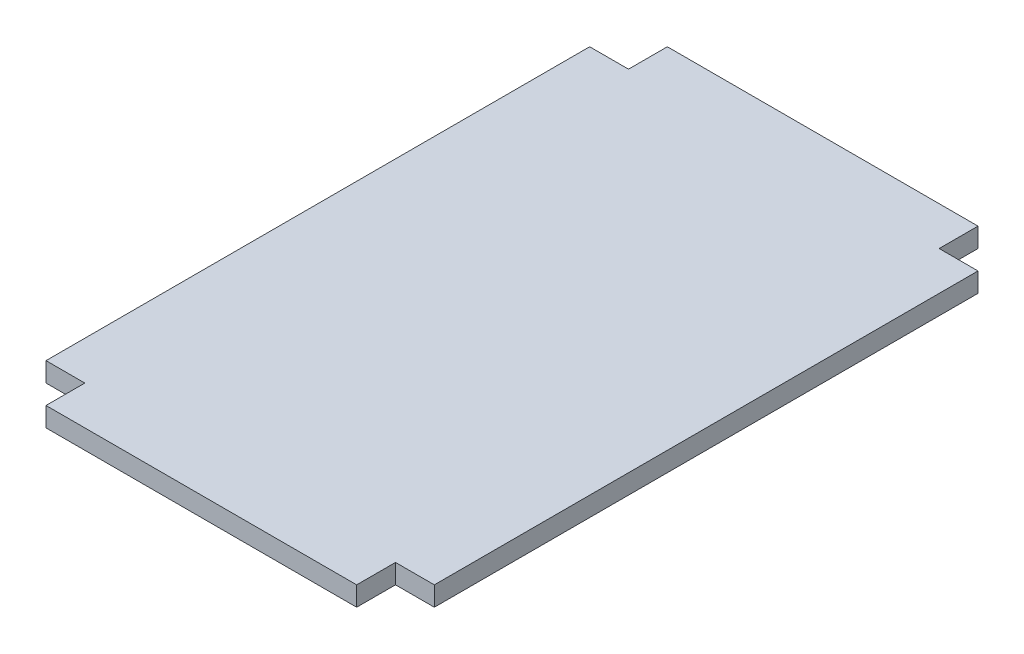
SolidWorks part; units mm, degrees
material "Oak"
ref_plane "Front Plane" through (0, 0, 0) normal (0, 0, 1) x (1, 0, 0)
ref_plane "Top Plane" through (0, 0, 0) normal (0, 1, 0) x (1, 0, 0)
ref_plane "Right Plane" through (0, 0, 0) normal (1, 0, 0) x (0, 0, -1)
sketch "Sketch1" plane through (0, 0, 0) normal (0, 1, 0) x (1, 0, 0)
  line L0 (-194.7505, 375.2161) -> (-194.7505, -158.1839)
  line L1 (-194.7505, -158.1839) -> (-156.6505, -158.1839)
  line L2 (-156.6505, -158.1839) -> (-156.6505, -196.2839)
  line L3 (-156.6505, -196.2839) -> (148.1495, -196.2839)
  line L4 (148.1495, -196.2839) -> (148.1495, -158.1839)
  line L5 (148.1495, -158.1839) -> (186.2495, -158.1839)
  line L6 (186.2495, -158.1839) -> (186.2495, 375.2161)
  line L7 (186.2495, 375.2161) -> (148.1495, 375.2161)
  line L8 (148.1495, 375.2161) -> (148.1495, 413.3161)
  line L9 (148.1495, 413.3161) -> (-156.6505, 413.3161)
  line L10 (-156.6505, 413.3161) -> (-156.6505, 375.2161)
  line L11 (-156.6505, 375.2161) -> (-194.7505, 375.2161)
  dimension "D1" = 609.6
  dimension "D2" = 304.8
  dimension "D3" = 304.8
  dimension "D4" = 38.1
  dimension "D5" = 38.1
  dimension "D6" = 38.1
  dimension "D7" = 38.1
  dimension "D8" = 38.1
  dimension "D9" = 38.1
  dimension "D10" = 38.1
extrude "Boss-Extrude1" add sketch "Sketch1" along normal blind 19.05
